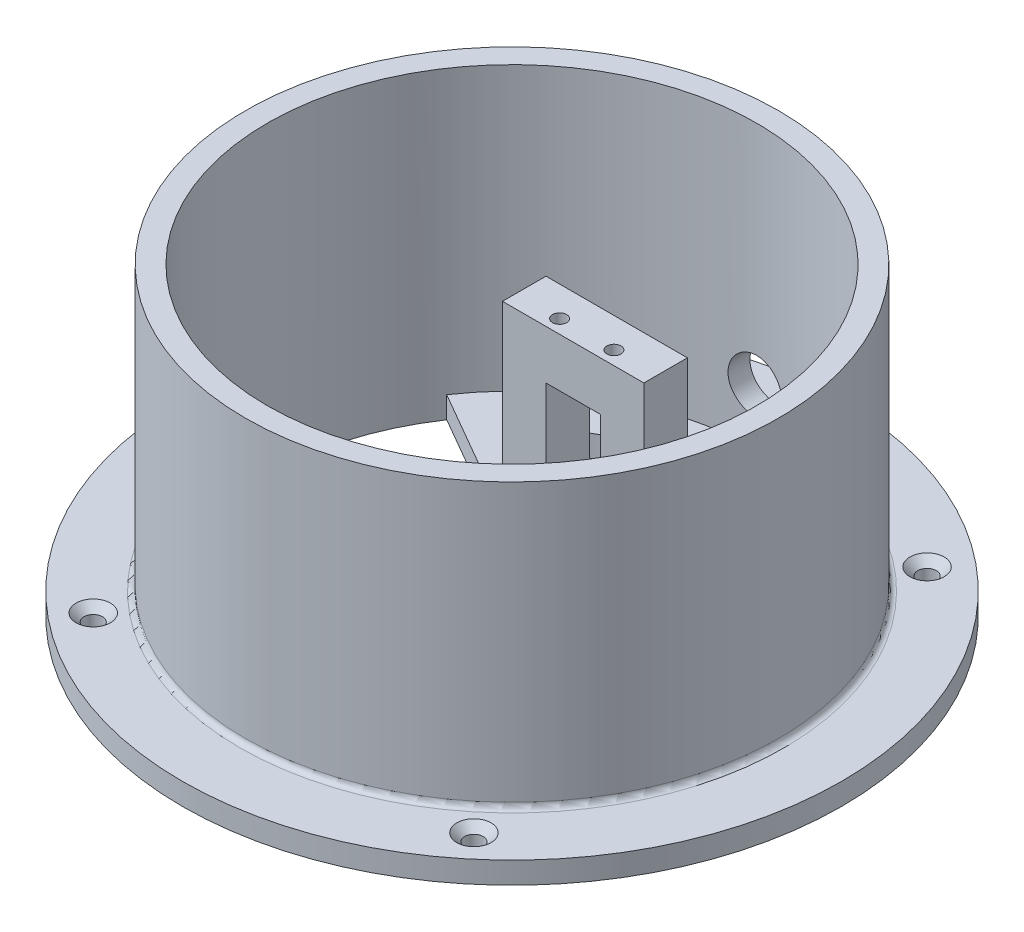
SolidWorks part; units mm, degrees
ref_plane "前视基准面" through (0, 0, 0) normal (0, 0, 1) x (1, 0, 0)
ref_plane "上视基准面" through (0, 0, 0) normal (0, 1, 0) x (1, 0, 0)
ref_plane "右视基准面" through (0, 0, 0) normal (1, 0, 0) x (0, 0, -1)
sketch "草图1" plane through (0, 0, 0) normal (0, 1, 0) x (1, 0, 0)
  circle A0 centre (0, 0) radius 45
  circle A1 centre (0, 0) radius 60.625
  dimension "D1" = 90
  dimension "D2" = 121.25
extrude "凸台-拉伸1" add sketch "草图1" along normal blind 4
sketch "草图2" plane through (0, 4, 0) normal (0, 1, 0) x (1, 0, 0)
  circle A0 centre (0, 0) radius 45 construction
  circle A1 centre (0, 0) radius 45
  circle A2 centre (0, 0) radius 49
  dimension "D1" = 4
extrude "凸台-拉伸2" add sketch "草图2" along normal blind 52
sketch "草图3" plane through (0, 0, 0) normal (1, 0, 0) x (0, 0, -1)
  line L0 (-46.75, 38) -> (-31.75, 38)
  line L1 (-31.75, 38) -> (-31.75, 30)
  line L2 (-31.75, 30) -> (-46.75, 30)
  line L3 (-46.75, 30) -> (-46.75, 38)
  line L4 (-45, 56) -> (-45, 0)
  line L5 (-31.75, 30) -> (-45, 16.75)
  line L6 (-45, 0) -> (45, 0) construction
  line L7 (11.25, 38) -> (19.25, 38)
  line L8 (11.25, 38) -> (11.25, 0)
  line L9 (11.25, 0) -> (19.25, 0)
  line L10 (19.25, 38) -> (19.25, 0)
  line L11 (15.25, 0) -> (15.25, 38) construction
  line L12 (11.25, 19) -> (19.25, 19) construction
  line L13 (49, 56) -> (-49, 56) construction
  line L14 (45, 56) -> (-45, 56) construction
  point P8 (15.25, 19)
  point P18 (-31.75, 34)
  dimension "D1" = 8
  dimension "D2" = 11.25
  dimension "D3" = 18
  dimension "D4" = 43
  dimension "D5" = 45
  dimension "D6" = 15
  dimension "D7" = 26
  dimension "D8" = 8
extrude "凸台-拉伸3" add sketch "草图3" along normal mid plane 26 separate body contours L0 L4 L2 L1 | L5 L2 L4 | L10 L7 L8 L9 region at (0, 34, 38.375) region at (0, 25.5833, 40.5833) region at (0, 19, -15.25)
sketch "草图4" plane through (0, 0, -11.25) normal (0, 0, 1) x (1, 0, 0)
  line L1 (-5, 29) -> (5, 29)
  line L2 (-5, 29) -> (-5, 5)
  line L3 (-5, 5) -> (5, 5)
  line L4 (5, 29) -> (5, 5)
  line L5 (0, 5) -> (0, 29) construction
  line L6 (-5, 17) -> (5, 17) construction
  line L9 (-60.625, 0) -> (60.625, 0) construction
  line L10 (13, 38) -> (-13, 38) construction
  point P0 (0, 17)
  dimension "D1" = 10
  dimension "D2" = 9
  dimension "D3" = 5
extrude "切除-拉伸1" cut sketch "草图4" against normal up to next (8 mm away)
sketch "草图5" plane through (0, 0, -11.25) normal (0, 0, 1) x (1, 0, 0)
  line L0 (0, 38) -> (0, 0) construction
  line L1 (-45, 0) -> (45, 0) construction
  circle A0 centre (0, 14) radius 5
  dimension "D1" = 10
  dimension "D2" = 14
extrude "切除-拉伸2" cut sketch "草图5" against normal blind 66
sketch "草图6" plane through (0, 38, 0) normal (0, 1, 0) x (1, 0, 0)
  line L0 (-5, 13.75) -> (5, 13.75) construction
  line L1 (-5, -34.25) -> (5, -34.25) construction
  line L2 (13, -31.75) -> (-13, -31.75) construction
  circle A0 centre (-5, 13.75) radius 1.3
  circle A1 centre (5, 13.75) radius 1.3
  circle A2 centre (5, -34.25) radius 1.3
  circle A3 centre (-5, -34.25) radius 1.3
  dimension "D1" = 2.6
  dimension "D2" = 5
  dimension "D3" = 10
  dimension "D4" = 2.5
  dimension "D5" = 10
  dimension "D6" = 48
extrude "切除-拉伸3" cut sketch "草图6" against normal blind 7.2
sketch "草图7" plane through (0, 0, 0) normal (0, -1, 0) x (1, 0, 0)
  line L0 (-19.5167, -24.25) -> (19.5167, -24.25)
  line L1 (13, -11.25) -> (-13, -11.25) construction
  line L2 (13, -11.25) -> (-13, -11.25)
  line L3 (-13, -11.25) -> (-37.2484, -25.2498)
  line L4 (0, 0) -> (0, -23.8419) construction
  line L5 (13, -11.25) -> (37.2484, -25.2498)
  line L6 (-19.5167, -24.25) -> (-24.9065, -27.3618)
  line L7 (19.5167, -24.25) -> (24.9065, -27.3618)
  line L9 (13, -19.25) -> (-13, -19.25) construction
  line L10 (10.8564, -19.25) -> (24.9065, -27.3618) construction
  line L11 (-10.8564, -19.25) -> (-24.9065, -27.3618) construction
  line L12 (10.8564, -19.25) -> (-10.8564, -19.25) construction
  circle A0 centre (0, 0) radius 45 construction
  arc A1 (-37.2484, -25.2498) -> (37.2484, -25.2498) centre (0, 0) ccw
  arc A2 (-24.9065, -27.3618) -> (24.9065, -27.3618) centre (0, 0) ccw
  dimension "D1" = 60
  dimension "D3" = 5
  dimension "D2" = 8
extrude "凸台-拉伸6" add sketch "草图7" against normal blind 4
sketch "草图8" plane through (0, 4, 0) normal (0, 1, 0) x (1, 0, 0)
  line L1 (-35, 42) -> (35, 42) construction
  line L2 (-35, 42) -> (-35, -42) construction
  line L3 (-35, -42) -> (35, -42) construction
  line L4 (35, 42) -> (35, -42) construction
  line L5 (0, -42) -> (0, 42) construction
  line L6 (-35, 0) -> (35, 0) construction
  point P0 (0, 0)
  dimension "D1" = 84
  dimension "D2" = 70
hole_wizard "M3 锥坑平头螺钉的锥形沉头孔1" positions "3D草图1" profile "草图9" countersink size "M3" standard "DIN"
sketch3d "3D草图1"
  line L0 (-35, 4, -42) -> (35, 4, -42) construction
  point P0 (-35, 4, -42)
  point P3 (34.3256, 4, -42)
  point P7 (35, 4, 42)
  point P10 (-35, 4, 42)
sketch "草图9" plane through (-35, 4, -42) normal (1, 0, 0) x (0, 0, 1)
  line L0 (0, 0) -> (0, 5.0215)
  line L1 (0, 5.0215) -> (1.7, 4)
  line L2 (1.7, 4) -> (1.7, 1.45)
  line L3 (1.7, 1.45) -> (3.15, 0)
  line L5 (3.15, 0) -> (0, 0)
  line L6 (-1.7, 1.45) -> (-3.15, 0) construction
  line L10 (0, 5.0215) -> (-1.7, 4) construction
  line L11 (0, -6.35) -> (0, 107.95) construction
  dimension "孔直径" = 3.4
  dimension "孔深度" = 4
  dimension "近端锥形沉头孔直径" = 6.3
  dimension "近端锥形沉头孔角度" = 90
  dimension "导头角度" = 118
fillet "圆角1" radius 1 1 edges at (0, 4, 49)
